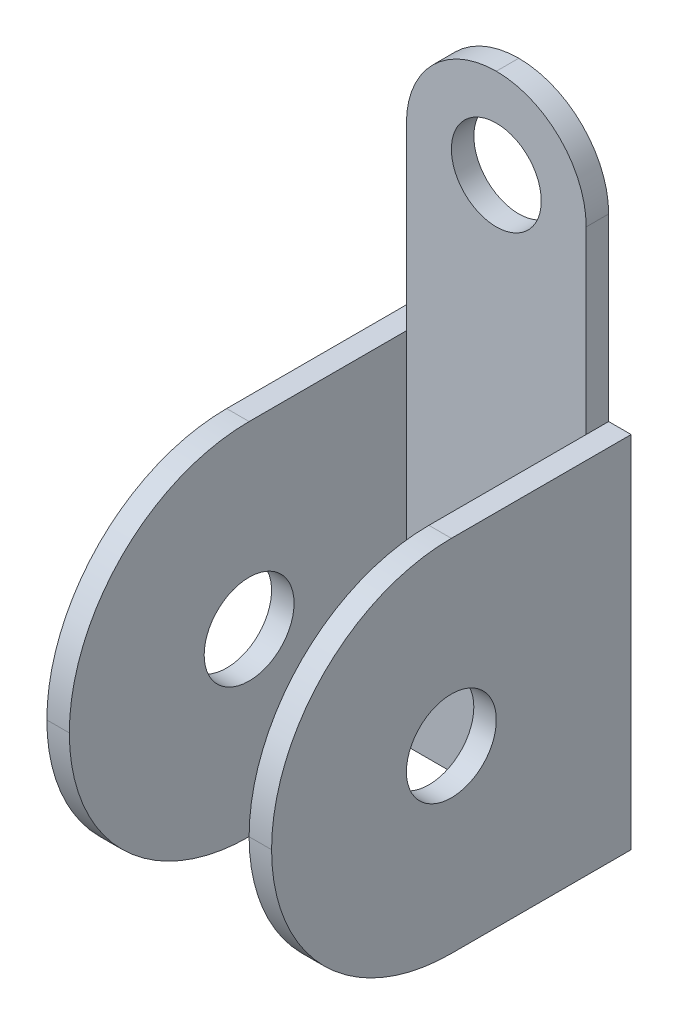
SolidWorks part; units mm, degrees
ref_plane "Front Plane" through (0, 0, 0) normal (0, 0, 1) x (1, 0, 0)
ref_plane "Top Plane" through (0, 0, 0) normal (0, 1, 0) x (1, 0, 0)
ref_plane "Right Plane" through (0, 0, 0) normal (1, 0, 0) x (0, 0, -1)
sketch "Sketch1" plane through (0, 0, 0) normal (0, 0, 1) x (1, 0, 0)
  line L0 (-6.35, 12.7) -> (-6.35, -12.7)
  line L1 (7.9375, 12.7) -> (-7.9375, 12.7)
  line L2 (7.9375, 12.7) -> (7.9375, -12.7)
  line L3 (7.9375, -12.7) -> (-7.9375, -12.7)
  line L4 (-7.9375, 12.7) -> (-7.9375, -12.7)
  line L5 (7.9375, 12.7) -> (-7.9375, -12.7) construction
  line L6 (7.9375, -12.7) -> (-7.9375, 12.7) construction
  line L7 (6.35, 12.7) -> (6.35, -12.7)
  line L8 (-7.9375, 0) -> (-6.35, 0) construction
  line L9 (6.35, 0) -> (7.9375, 0) construction
  line L10 (-6.35, 12.7) -> (-6.35, 31.75)
  line L11 (-6.35, 31.75) -> (6.35, 31.75)
  line L12 (6.35, 31.75) -> (6.35, 12.7)
  line L13 (0, 12.7) -> (0, 31.75) construction
  circle A0 centre (0, 25.4) radius 3.175
  point P0 (0, 0)
  point P18 (0, 25.4)
  dimension "D6" = 6.35
  dimension "D1" = 1.5875
  dimension "D2" = 25.4
  dimension "D3" = 12.7
  dimension "D4" = 12.7
  dimension "D5" = 6.35
extrude "Boss-Extrude1" add sketch "Sketch1" along normal blind 1.5875 contours L7 L1 L0 L3 | L12 L11 L10 L1 A0 region at (0, 0, 0) region at (0, 21.7468, 0)
extrude "Boss-Extrude2" add sketch "Sketch1<3>" along normal blind 25.4 contours L1 L4 L3 L0 | L1 L7 L3 L2 region at (-7.1438, 0, 0) region at (7.1437, 0, 0)
sketch "Sketch1<3>" plane through (0, 0, 0) normal (0, 0, 1) x (1, 0, 0) same geometry as "Sketch1"
sketch "Sketch2" plane through (-7.9375, 0, 0) normal (-1, 0, 0) x (0, 0, 1)
  line L1 (0, 12.7) -> (25.4, 12.7) construction
  line L2 (0, 12.7) -> (0, -12.7) construction
  line L3 (0, -12.7) -> (25.4, -12.7) construction
  line L4 (25.4, 12.7) -> (25.4, -12.7) construction
  line L5 (0, 12.7) -> (25.4, -12.7) construction
  line L6 (0, -12.7) -> (25.4, 12.7) construction
  circle A0 centre (12.7, 0) radius 3.175
  point P4 (12.7, 0)
  point P9 (0.5061, 12.1939)
  dimension "D1" = 6.35
extrude "Cut-Extrude1" cut sketch "Sketch2" against normal through all
fillet "Fillet1" radius 12.7 4 edges at (-7.1438, -12.7, 25.4) (7.1437, -12.7, 25.4) (7.1437, 12.7, 25.4) (-7.1438, 12.7, 25.4)
fillet "Fillet2" radius 6.35 2 edges at (-6.35, 31.75, 0.7937) (6.35, 31.75, 0.7937)
